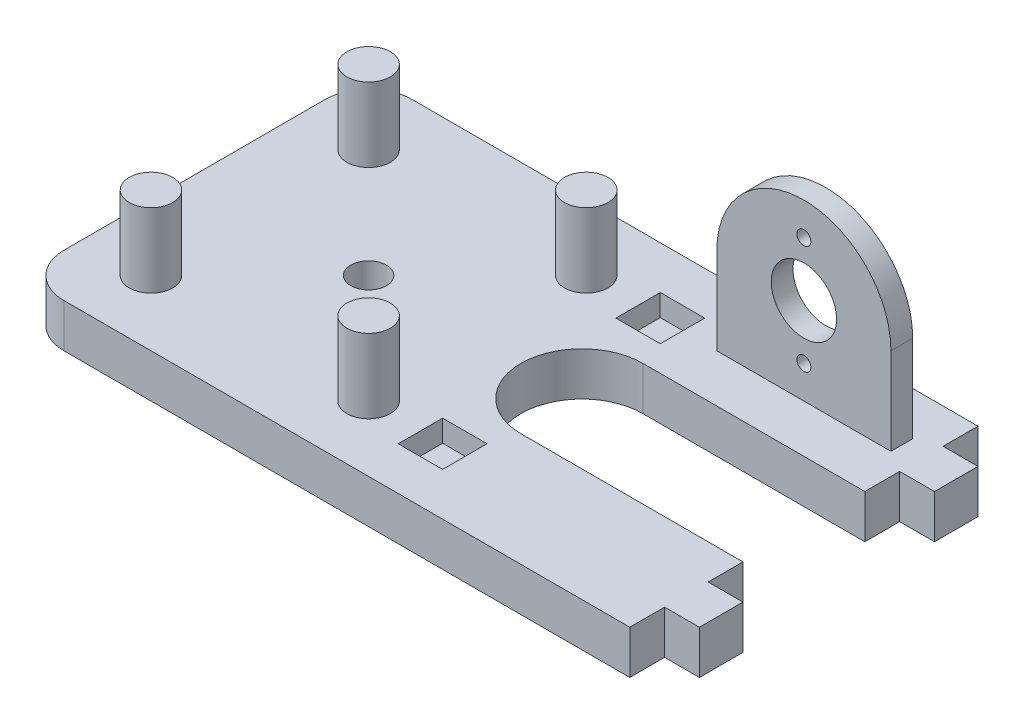
SolidWorks part; units mm, degrees
ref_plane "正面" through (0, 0, 0) normal (0, 0, 1) x (1, 0, 0)
ref_plane "平面" through (0, 0, 0) normal (0, 1, 0) x (1, 0, 0)
ref_plane "右側面" through (0, 0, 0) normal (1, 0, 0) x (0, 0, -1)
sketch "ｽｹｯﾁ1" plane through (0, 0, 0) normal (0, 1, 0) x (1, 0, 0)
  line L0 (70, 14) -> (70, 40)
  line L1 (-70, -40) -> (70, -40)
  line L2 (-70, -40) -> (-70, 40)
  line L3 (-70, 40) -> (70, 40)
  line L4 (70, -40) -> (70, -14)
  line L5 (-70, -40) -> (70, 40) construction
  line L6 (-70, 40) -> (70, -40) construction
  line L7 (70, 14) -> (5, 14)
  line L9 (70, -14) -> (5, -14)
  line L10 (5, 14) -> (5, -14)
  line L11 (-70, 40) -> (35285.3391, -35315.3391) construction
  line L12 (-70, -40) -> (35285.3391, 35315.3391) construction
  circle A0 centre (-30, 0) radius 4.1
  point P0 (0, 0)
  point P17 (-30, 0)
  dimension "D5" = 8.2
  dimension "D1" = 80
  dimension "D2" = 140
  dimension "D3" = 28
  dimension "D4" = 65
  dimension "D6" = 45
  dimension "D7" = 45
extrude "ﾎﾞｽ - 押し出し1" add sketch "ｽｹｯﾁ1" along normal blind 10
sketch "ｽｹｯﾁ2" plane through (0, 10, 0) normal (0, 1, 0) x (1, 0, 0)
  line L2 (-70, 40) -> (10, -40) construction
  line L4 (70, 40) -> (-70, 40) construction
  circle A0 centre (-55, 25) radius 5
  circle A1 centre (-5, 25) radius 5
  circle A2 centre (-5, -25) radius 5
  circle A3 centre (-55, -25) radius 5
  dimension "D1" = 10
  dimension "D2" = 50
  dimension "D3" = 50
  dimension "D4" = 25
  dimension "D5" = 45
extrude "ﾎﾞｽ - 押し出し2" add sketch "ｽｹｯﾁ2" along normal blind 17
fillet "ﾌｨﾚｯﾄ1" radius 10 2 edges at (-70, 5, -40) (-70, 5, 40)
fillet "ﾌｨﾚｯﾄ2" 2 edges at (5, 5, 14) (5, 5, -14) type full round first side face at (37.5, 5, 14) second side face at (37.5, 5, -14) middle face at (5, 5, 0)
sketch "ｽｹｯﾁ4" plane through (70, 0, 0) normal (1, 0, 0) x (0, 0, -1)
  line L0 (-40, 0) -> (-14, 0) construction
  line L1 (-32, 0) -> (-22, 0)
  line L2 (-32, 0) -> (-32, 10)
  line L3 (-32, 10) -> (-22, 10)
  line L4 (-22, 0) -> (-22, 10)
  line L5 (-40, 10) -> (-14, 10) construction
  line L6 (14, 0) -> (40, 0) construction
  line L7 (22, 0) -> (32, 0)
  line L8 (22, 0) -> (22, 10)
  line L9 (22, 10) -> (32, 10)
  line L10 (32, 0) -> (32, 10)
  line L11 (14, 10) -> (40, 10) construction
  point P16 (-27, 0)
  point P17 (-27, 0)
  point P18 (27, 0)
  point P19 (27, 0)
extrude "ﾎﾞｽ - 押し出し3" add sketch "ｽｹｯﾁ4" along normal blind 8
sketch "ｽｹｯﾁ5" plane through (0, 10, 0) normal (0, 1, 0) x (1, 0, 0)
  line L1 (65, 25) -> (25, 25)
  line L2 (65, 25) -> (65, 30)
  line L3 (65, 30) -> (25, 30)
  line L4 (25, 25) -> (25, 30)
  line L5 (19, 14) -> (70, 14) construction
  line L6 (70, 14) -> (70, 22) construction
  dimension "D1" = 5
  dimension "D2" = 40
  dimension "D3" = 11
  dimension "D4" = 5
extrude "ﾎﾞｽ - 押し出し4" add sketch "ｽｹｯﾁ5" along normal blind 40
fillet "ﾌｨﾚｯﾄ3" 2 edges at (65, 50, -27.5) (25, 50, -27.5) type full round first side face at (65, 30, -27.5) second side face at (25, 30, -27.5) middle face at (45, 50, -27.5)
sketch "ｽｹｯﾁ6" plane through (0, 0, -25) normal (0, 0, 1) x (1, 0, 0)
  circle A0 centre (45, 30) radius 7.5
  circle A1 centre (45, 42.5) radius 1.6
  circle A2 centre (45, 17.5) radius 1.6
  arc A4 (65, 30) -> (25, 30) centre (45, 30) ccw construction
  dimension "D2" = 15
  dimension "D3" = 3.2
  dimension "D1" = 25
  dimension "D4" = 12.5
extrude "ｶｯﾄ - 押し出し1" cut sketch "ｽｹｯﾁ6" against normal through all
sketch "ｽｹｯﾁ7" plane through (0, 10, 0) normal (0, 1, 0) x (1, 0, 0)
  line L1 (6.9, 30.1) -> (17.1, 30.1)
  line L2 (6.9, 30.1) -> (6.9, 19.9)
  line L3 (6.9, 19.9) -> (17.1, 19.9)
  line L4 (17.1, 30.1) -> (17.1, 19.9)
  line L5 (6.9, 30.1) -> (17.1, 19.9) construction
  line L6 (6.9, 19.9) -> (17.1, 30.1) construction
  line L7 (6.9, -19.9) -> (17.1, -19.9)
  line L8 (6.9, -19.9) -> (6.9, -30.1)
  line L9 (6.9, -30.1) -> (17.1, -30.1)
  line L10 (17.1, -19.9) -> (17.1, -30.1)
  line L11 (6.9, -19.9) -> (17.1, -30.1) construction
  line L12 (6.9, -30.1) -> (17.1, -19.9) construction
  point P0 (12, 25)
  point P4 (12, -25)
  point P11 (0, 0)
  dimension "D1" = 10.2
  dimension "D2" = 25
  dimension "D3" = 25
  dimension "D4" = 12
extrude "ｶｯﾄ - 押し出し2" cut sketch "ｽｹｯﾁ7" against normal blind 5
